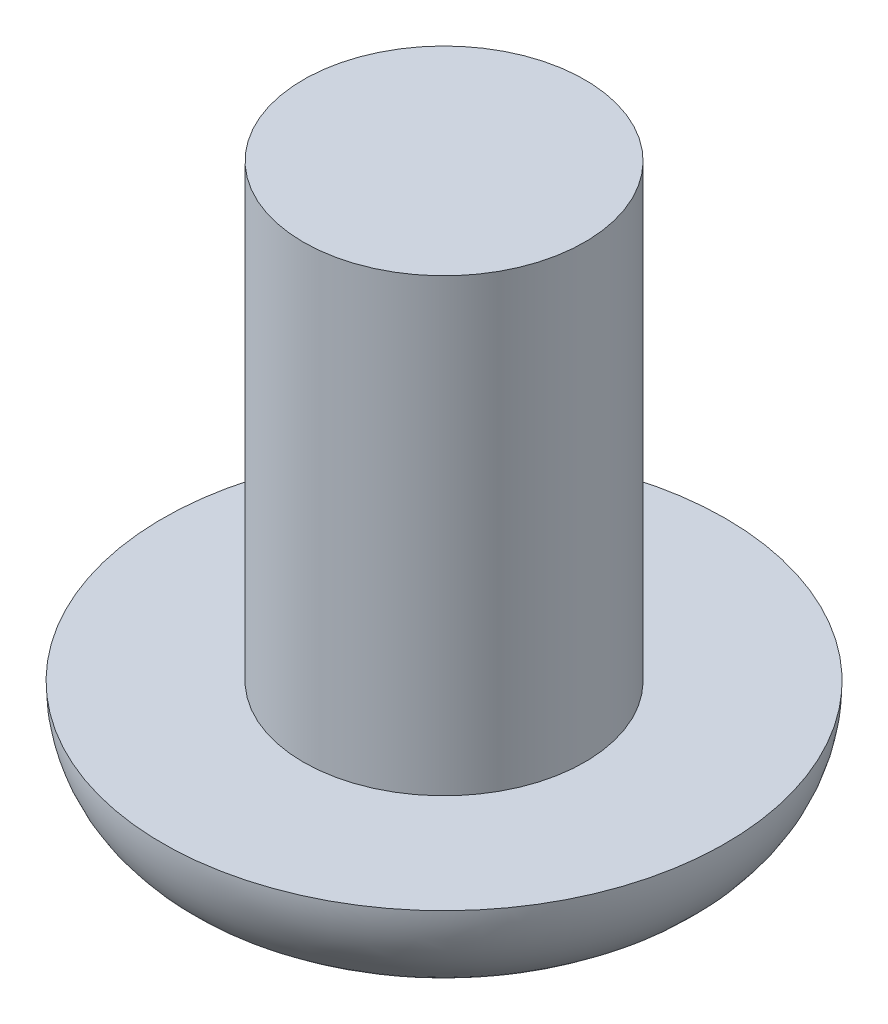
SolidWorks part; units mm, degrees
ref_plane "Front Plane" through (0, 0, 0) normal (0, 0, 1) x (1, 0, 0)
ref_plane "Top Plane" through (0, 0, 0) normal (0, 1, 0) x (1, 0, 0)
ref_plane "Right Plane" through (0, 0, 0) normal (1, 0, 0) x (0, 0, -1)
sketch "Sketch1" plane through (0, 0, 0) normal (0, 1, 0) x (1, 0, 0)
  circle A0 centre (0, 0) radius 2.5
  dimension "D1" = 5
extrude "Boss-Extrude1" add sketch "Sketch1" along normal blind 8 contours A0
sketch "Sketch2" plane through (0, 0, 0) normal (0, -1, 0) x (1, 0, 0)
  circle A0 centre (0, 0) radius 5
  dimension "D1" = 10
extrude "Boss-Extrude2" add sketch "Sketch2" along normal blind 2
fillet "Fillet1" radius 2 1 edges at (0, -2, -5)
sketch "Sketch3" plane through (0, -2, 0) normal (0, -1, 0) x (1, 0, 0)
  line L0 (0.375, 0.375) -> (1.5, 0.375)
  line L1 (-0.375, -1.5) -> (0.375, -1.5)
  line L2 (-0.375, -1.5) -> (-0.375, -0.375)
  line L3 (-0.375, 1.5) -> (0.375, 1.5)
  line L4 (0.375, -1.5) -> (0.375, -0.375)
  line L7 (-1.5, -0.375) -> (-0.375, -0.375)
  line L8 (-1.5, -0.375) -> (-1.5, 0.375)
  line L9 (-1.5, 0.375) -> (-0.375, 0.375)
  line L10 (1.5, -0.375) -> (1.5, 0.375)
  line L15 (0.375, 0.375) -> (0.375, 1.5)
  line L16 (0.375, -0.375) -> (1.5, -0.375)
  line L17 (-0.375, 0.375) -> (-0.375, 1.5)
  point P0 (0, 0)
  point P6 (0, 0)
  dimension "D1" = 3
  dimension "D2" = 0.75
extrude "Cut-Extrude1" cut sketch "Sketch3" against normal blind 1 draft 15
